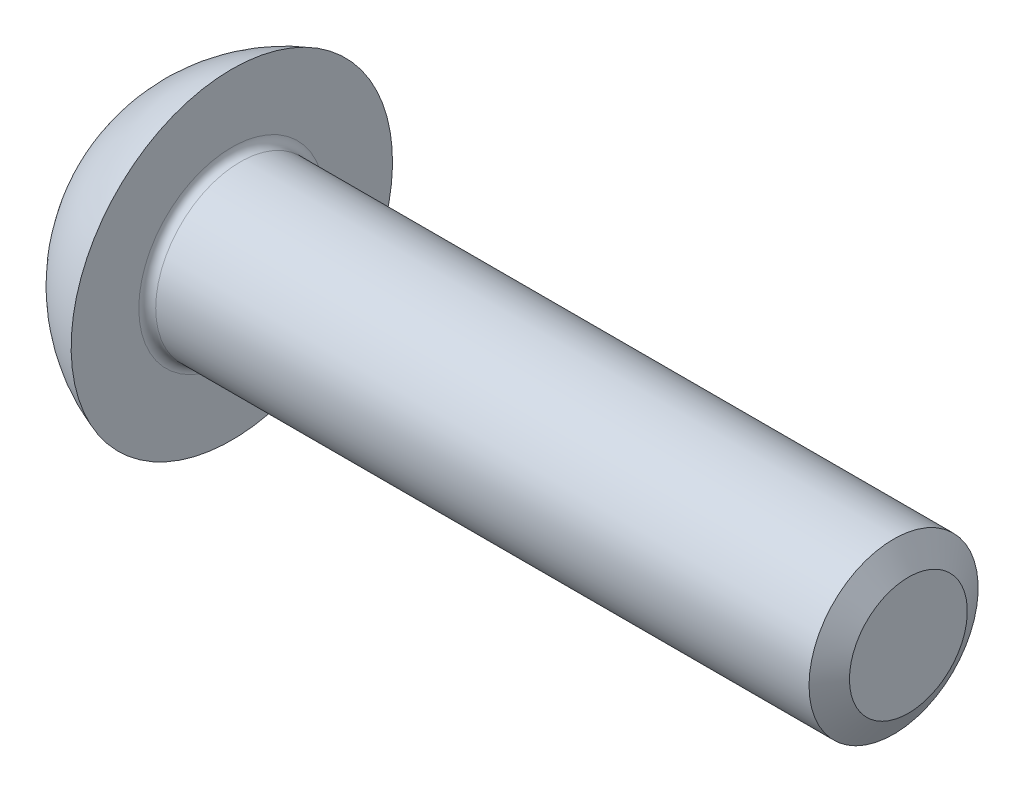
SolidWorks part; units mm, degrees
ref_plane "前视基准面" through (0, 0, 0) normal (0, 0, 1) x (1, 0, 0)
ref_plane "上视基准面" through (0, 0, 0) normal (0, 1, 0) x (1, 0, 0)
ref_plane "右视基准面" through (0, 0, 0) normal (1, 0, 0) x (0, 0, -1)
sketch "尺寸草图" plane through (0, 0, 0) normal (0, 0, 1) x (1, 0, 0)
  line L0 (0, 0) -> (16, 0) construction
  line L1 (16, 0) -> (16, 2) construction
  line L2 (16, 2) -> (15.3, 2) construction
  line L3 (0, 0) -> (0, 3.8) construction
  point P3 (1.4, 0)
  point P6 (16, 2.35)
  point P7 (0, 0.93)
  point P9 (2.2, 0)
  point P10 (2.4, 0)
  point P11 (16, 1.25)
  point P12 (3.7, 0)
  point P13 (4, 0)
  point P14 (16, 18.35)
  dimension "l" = 16
  dimension "d" = 4
  dimension "P" = 0.7
  dimension "a" = 1.4
  dimension "da" = 4.7
  dimension "dk" = 7.6
  dimension "e" = 2.87
  dimension "K" = 2.2
  dimension "r" = 0.2
  dimension "s" = 2.5
  dimension "t" = 1.3
  dimension "w" = 0.3
  dimension "zslwx" = 16
sketch "草图1" plane through (0, 0, 0) normal (0, 0, 1) x (1, 0, 0)
  line L0 (-18.2, 0) -> (0, 0) construction
  line L1 (0, 2) -> (-15.8, 2)
  line L2 (-16, 2.2) -> (-16, 3.8)
  line L3 (-18.2, 0) -> (-18.2, 2)
  line L4 (0, 2) -> (0, 0)
  line L5 (-18.2, 0) -> (0, 0)
  arc A0 (-16, 3.8) -> (-18.2, 2) centre (-14.7273, 0) ccw
  arc A1 (-15.8, 2) -> (-16, 2.2) centre (-15.8, 2.2) cw
  point P10 (-16, 2)
  dimension "r" = 0.2
  dimension "d" = 4
  dimension "dk" = 7.6
  dimension "k" = 2.2
  dimension "l" = 16
revolve "旋转1" add sketch "草图1" angle 360 about L0
cosmetic thread "装饰螺纹线1" parameters "D1"=16, "D2"=3.44
sketch "草图2" plane through (-18.2, 0, 0) normal (-1, 0, 0) x (0, 0, 1)
  line L1 (0, 1.4434) -> (-1.25, 0.7217)
  line L2 (-1.25, 0.7217) -> (-1.25, -0.7217)
  line L3 (-1.25, -0.7217) -> (0, -1.4434)
  line L4 (0, -1.4434) -> (1.25, -0.7217)
  line L5 (1.25, -0.7217) -> (1.25, 0.7217)
  line L6 (1.25, 0.7217) -> (0, 1.4434)
  circle A0 centre (0, 0) radius 1.25 construction
  dimension "s" = 2.5
extrude "切除-拉伸1" cut sketch "草图2" against normal blind 2.2
sketch "草图6" plane through (0, 0, 0) normal (0, 0, 1) x (1, 0, 0)
  line L0 (-16.9, 1.4434) -> (-16, 0)
  line L1 (-15.63, 1.4434) -> (-15.63, 0)
  line L2 (-15.63, 1.4434) -> (-16.9, 1.4434)
  line L3 (-18.2, 0) -> (-16, 0) construction
  line L4 (-15.63, 0) -> (-16, 0)
  line L5 (-18.2, 0) -> (-21.07, 0) construction
  dimension "t" = 1.3
  dimension "e-s" = 0.37
  dimension "k" = 2.2
  dimension "e" = 2.87
revolve "旋转2" add sketch "草图6" angle 360 about L3
sketch "草图7" plane through (0, 0, 0) normal (0, 0, 1) x (1, 0, 0)
  line L3 (-18.2, 1.4434) -> (-17.83, 0)
  line L4 (-18.2, 0) -> (-17.83, 0) construction
  line L7 (-18.2, 1.4434) -> (-18.2, 0)
  line L8 (-18.2, 0) -> (-17.83, 0)
  dimension "e-s" = 0.37
revolve "切除-旋转5" cut sketch "草图7" angle 360 about L4
sketch "草图4" plane through (0, 0, 0) normal (0, 0, 1) x (1, 0, 0)
  line L0 (-0.35, 2) -> (0, 1.3938)
  line L1 (-0.35, 2) -> (0.35, 2)
  line L2 (0.35, 2) -> (0, 1.3938)
  line L4 (0, -2) -> (0, 2) construction
  line L5 (-0.35, 0) -> (0.35, 0) construction
  dimension "d" = 2
  dimension "p" = 0.7
revolve "切除-旋转1" cut sketch "草图4" angle 360 about L5
ref_axis "基准轴1" through (-8.1887, 0, 0) along (1, 0, 0)
pattern_linear "阵列(线性)1" [suppressed] count 21 spacing 0.7 along (-1, 0, 0) of bodies 104
